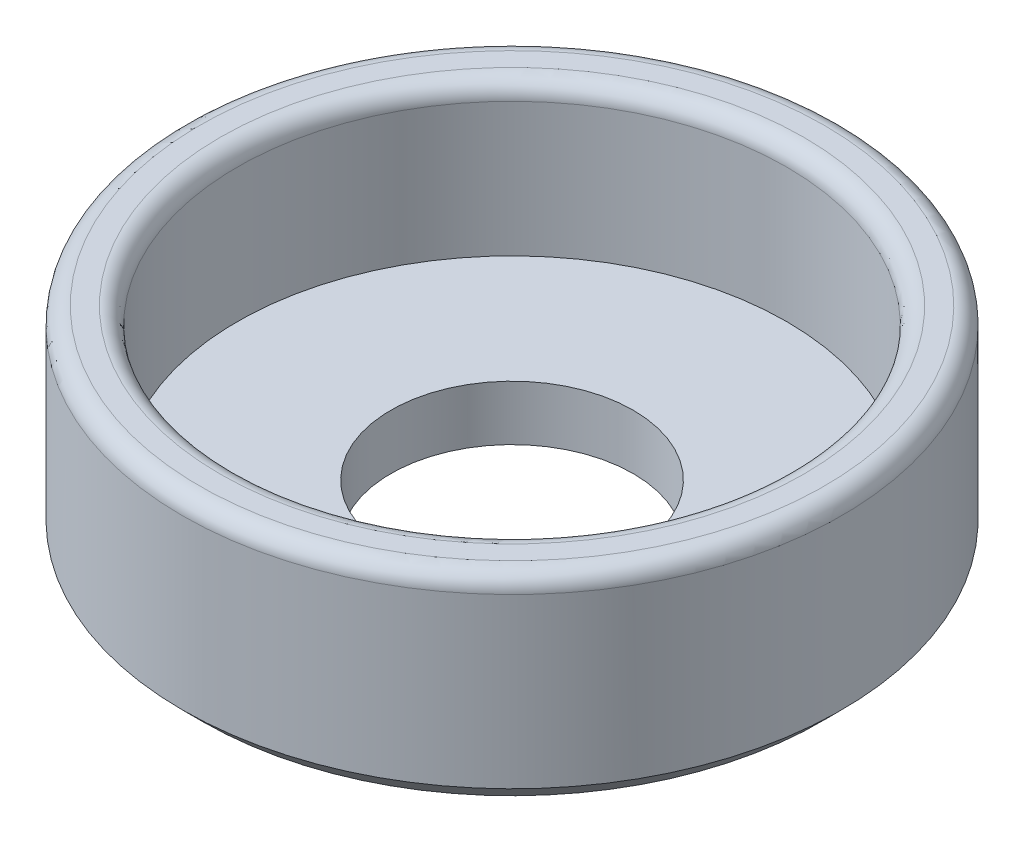
SolidWorks part; units mm, degrees
ref_plane "Front Plane" through (0, 0, 0) normal (0, 0, 1) x (1, 0, 0)
ref_plane "Top Plane" through (0, 0, 0) normal (0, 1, 0) x (1, 0, 0)
ref_plane "Right Plane" through (0, 0, 0) normal (1, 0, 0) x (0, 0, -1)
sketch "Sketch1" plane through (0, 0, 0) normal (0, 0, 1) x (1, 0, 0)
  line L0 (0, 0) -> (4.8, 0)
  line L1 (4.8, 0) -> (4.8, 3)
  line L2 (4.8, 3) -> (4, 3)
  line L3 (4, 3) -> (4, 0.8)
  line L4 (4, 0.8) -> (0, 0.8)
  line L5 (0, 0.8) -> (0, 0)
  point P3 (8.7359, 5.2463)
  dimension "D1" = 0.8
  dimension "D2" = 4
  dimension "D3" = 3
revolve "Revolve1" add sketch "Sketch1" angle 360 about L5
sketch "Sketch2" plane through (0, 0.8, 0) normal (0, 1, 0) x (1, 0, 0)
  circle A0 centre (0, 0) radius 1.765
  dimension "D1" = 3.53
extrude "Cut-Extrude1" cut sketch "Sketch2" against normal through all
fillet "Fillet1" radius 0.25 2 edges at (0, 3, 4) (0, 3, 4.8)
chamfer "Chamfer1" distance 0.3 angle 45 1 edges at (0, 0, 4.8)
